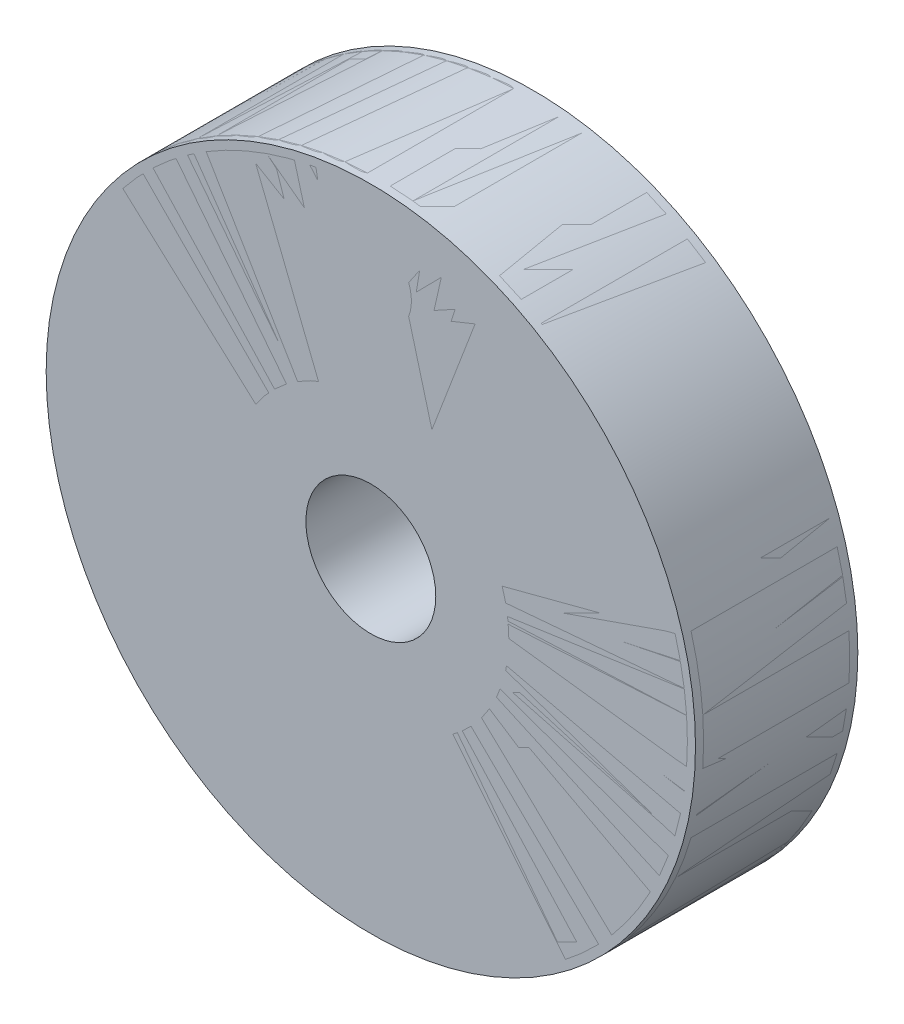
SolidWorks part; units mm, degrees
ref_plane "前视基准面" through (0, 0, 0) normal (0, 0, 1) x (1, 0, 0)
ref_plane "上视基准面" through (0, 0, 0) normal (0, 1, 0) x (1, 0, 0)
ref_plane "右视基准面" through (0, 0, 0) normal (1, 0, 0) x (0, 0, -1)
sketch "草图1" plane through (0, 0, 0) normal (0, 0, 1) x (1, 0, 0)
  circle A0 centre (0, 0) radius 20
  dimension "D1" = 40
extrude "凸台-拉伸1" add sketch "草图1" along normal blind 10
sketch "草图2" plane through (0, 0, 0) normal (0, 0, 1) x (1, 0, 0)
  circle A0 centre (0, 0) radius 4
  dimension "D1" = 8
extrude "切除-拉伸1" cut sketch "草图2" along normal blind 14
sketch "草图3" plane through (0, 0, 0) normal (0, 0, 1) x (1, 0, 0)
  circle A0 centre (0, 0) radius 8
  dimension "D1" = 16
extrude "切除-拉伸2" cut sketch "草图3" along normal blind 4
sketch "草图4" plane through (0, 0, 0) normal (0, 0, 1) x (1, 0, 0)
  circle A0 centre (0, 0) radius 20
  dimension "D1" = 40
extrude "凸台-拉伸2" add sketch "草图4" along normal blind 10 separate body
sketch "草图5" plane through (0, 0, 10) normal (0, 0, 1) x (1, 0, 0)
  circle A0 centre (0, 0) radius 4
  dimension "D1" = 8
extrude "切除-拉伸3" cut sketch "草图5" against normal blind 10
sketch "草图6" plane through (0, 0, 10) normal (0, 0, 1) x (1, 0, 0)
  circle A0 centre (0, 0) radius 8
  dimension "D1" = 16
extrude "切除-拉伸4" cut sketch "草图6" against normal blind 4
sketch "草图7" plane through (0, 0, 10) normal (0, 0, 1) x (1, 0, 0)
  circle A1 centre (0, -14.9988) radius 2
  circle A2 centre (0, 15) radius 2
  dimension "D1" = 4
  dimension "D2" = 4
extrude "切除-拉伸5" cut sketch "草图7" against normal blind 10
fillet "圆角1" radius 0.5 2 edges at (20, 0, 10) (20, 0, 0)
chamfer "倒角1" distance 0.5 angle 45 1 edges at (8, 0, 10)
fillet "圆角2" radius 0.5 1 edges at (4, 0, 0)
chamfer "倒角3" distance 0.5 angle 45 4 edges at (2, -14.9988, 10) (2, 15, 10) (2, -14.9988, 0) (2, 15, 0)
